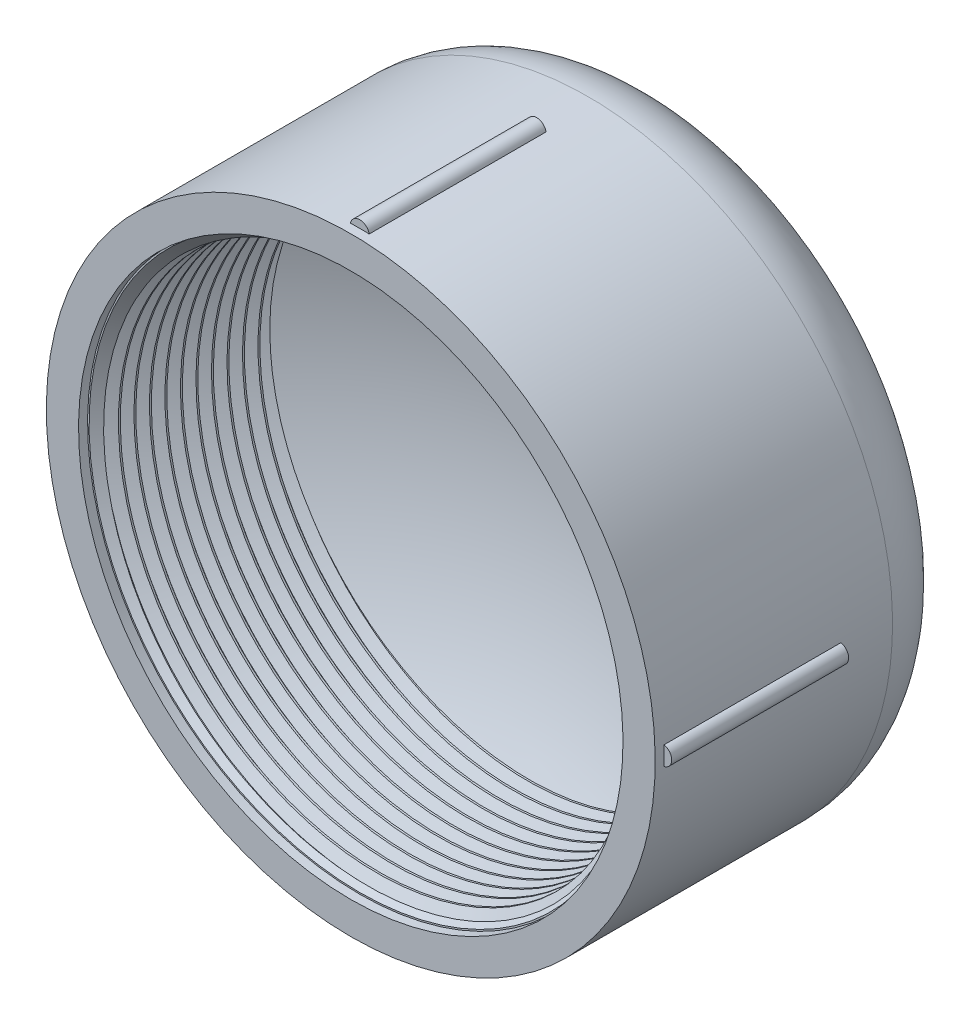
SolidWorks part; units mm, degrees
ref_plane "Front Plane" through (0, 0, 0) normal (0, 0, 1) x (1, 0, 0)
ref_plane "Top Plane" through (0, 0, 0) normal (0, 1, 0) x (1, 0, 0)
ref_plane "Right Plane" through (0, 0, 0) normal (1, 0, 0) x (0, 0, -1)
sketch "Sketch1" plane through (0, 0, 0) normal (1, 0, 0) x (0, 0, -1)
  line L0 (-37.719, 0) -> (37.719, 0) construction
  line L2 (-37.719, -57.4675) -> (-37.719, -64.262) construction
  line L3 (0.5524, 55.6734) -> (-0.381, 55.6734) construction
  line L4 (-0.381, 55.6734) -> (-0.381, 56.0468) construction
  line L5 (-37.719, -64.262) -> (22.6314, -64.262) construction
  line L6 (-37.719, 57.4675) -> (-37.719, 64.262) construction
  line L7 (-37.719, 64.262) -> (22.6314, 64.262) construction
  line L10 (0.5524, -55.6734) -> (-0.381, -55.6734) construction
  line L11 (-0.381, -55.6734) -> (-0.381, -56.0468) construction
  line L12 (-35.814, -57.15) -> (-0.381, -56.0468) construction
  line L13 (-35.814, 57.15) -> (-0.381, 56.0468) construction
  line L14 (-0.381, -55.6734) -> (-0.381, 55.6734) construction
  line L15 (-37.719, 57.4675) -> (-40.894, 57.4675) construction
  line L16 (-35.814, -57.15) -> (-35.814, -57.4675) construction
  line L17 (-35.814, -57.4675) -> (-37.719, -57.4675) construction
  line L18 (-35.814, 57.15) -> (-35.814, 57.4675) construction
  line L19 (-35.814, 57.4675) -> (-37.719, 57.4675) construction
  line L20 (-35.814, -57.15) -> (-35.814, 57.15) construction
  line L21 (-37.719, -57.4675) -> (-37.719, 0) construction
  line L22 (-37.719, 0) -> (-37.719, 57.4675) construction
  arc A0 (0.5524, -55.6734) -> (0.5524, 55.6734) centre (-106.6791, 0) ccw construction
  arc A5 (22.6314, -64.262) -> (22.6314, 64.262) centre (-106.6791, 0) ccw construction
  point P4 (0, 0)
  point P9 (-37.719, 0)
  point P30 (-35.814, 0)
  dimension "D1" = 1.783
  dimension "D2" = 1.783
  dimension "OD" = 128.524
  dimension "Body Cylindrical Length" = 60.3504
  dimension "D4" = 0.3734
  dimension "D5" = 0.9335
  dimension "NPT Pitch" = 3.175
  dimension "Thread OD" = 114.3
  dimension "Pilot Depth" = 1.905
  dimension "Pilot Dia" = 114.935
  dimension "Depth" = 37.338
  dimension "OAL" = 75.438
sketch "Sketch2" plane through (0, 0, 0) normal (1, 0, 0) x (0, 0, -1)
  line L21 (-37.719, -64.262) -> (22.6314, -64.262) construction
  line L22 (0.5524, -55.6734) -> (-0.381, -55.6734) construction
  line L23 (-0.381, -55.6734) -> (-0.381, -56.0468) construction
  line L24 (-35.814, -57.15) -> (-0.381, -56.0468) construction
  line L25 (-35.814, -57.15) -> (-35.814, -57.4675) construction
  line L26 (-35.814, -57.4675) -> (-37.719, -57.4675) construction
  line L27 (-37.719, -57.4675) -> (-37.719, -64.262) construction
  line L28 (-37.719, -64.262) -> (22.6314, -64.262)
  line L29 (0.5524, -55.6734) -> (-0.381, -55.6734)
  line L30 (-0.381, -55.6734) -> (-0.381, -56.0468)
  line L31 (-35.814, -57.15) -> (-0.381, -56.0468)
  line L32 (-35.814, -57.15) -> (-35.814, -57.4675)
  line L33 (-35.814, -57.4675) -> (-37.719, -57.4675)
  line L34 (-37.719, -57.4675) -> (-37.719, -64.262)
  line L35 (14.1436, 0) -> (37.719, 0)
  arc A1 (22.6314, -64.262) -> (22.6314, 64.262) centre (-106.6791, 0) ccw construction
  arc A2 (0.5524, -55.6734) -> (0.5524, 55.6734) centre (-106.6791, 0) ccw construction
  arc A6 (22.6314, -64.262) -> (37.719, 0) centre (-106.6791, 0) ccw
  arc A7 (0.5524, -55.6734) -> (14.1436, 0) centre (-106.6791, 0) ccw
revolve "Revolve1" add sketch "Sketch2" angle 360 about L0
fillet "Fillet1" radius 15.875 1 edges at (0, -64.262, -22.6314)
sketch "Sketch3" plane through (0, 0, 37.719) normal (0, 0, 1) x (1, 0, 0)
  circle A5 centre (0, 0) radius 57.15
  point P2 (0, 57.15)
  point P3 (-57.15, 0)
  point P4 (0, -57.15)
  point P5 (57.15, 0)
  dimension "D1" = 114.3
ref_plane "Plane1" through (0, 0, 35.814) normal (0, 0, 1) x (1, 0, 0)
sketch "Sketch4" plane through (0, 0, 35.814) normal (0, 0, 1) x (1, 0, 0)
  line L0 (-1.9844, 64.2314) -> (1.9844, 64.2314) construction
  line L1 (0, -64.262) -> (0, 64.262) construction
  line L3 (0, 64.262) -> (0, 65.8495) construction
  circle A0 centre (0, 0) radius 64.262 construction
  arc A1 (1.9844, 64.2314) -> (-1.9844, 64.2314) centre (0, 0) ccw
  arc A8 (-1.9844, 64.2314) -> (1.9844, 64.2314) centre (0, 63.8237) cw
  point P18 (0, 64.262)
  dimension "Rib Dia" = 3.9688
  dimension "Rib Height" = 1.5875
extrude "Boss-Extrude1" add sketch "Sketch4" against normal blind 37.338
pattern_circular "CirPattern1" count 4 over 360 about axis through (0, 0, 0) along (0, 0, 1) of "Boss-Extrude1"
sketch "Sketch5" plane through (0, 0, 35.814) normal (0, 0, 1) x (1, 0, 0)
  circle A1 centre (0, 0) radius 57.4675
  circle A2 centre (0, 0) radius 57.4675 construction
extrude "Boss-Extrude2" add sketch "Sketch5" against normal up to surface (35.433 mm away) contours A1 up to face at (0, -56.0468, 0.381)
sketch "Sketch6" plane through (0, 0, 35.814) normal (0, 0, 1) x (1, 0, 0)
  circle A0 centre (0, 0) radius 57.15
  dimension "D1" = 114.3
extrude "Boss-Extrude3" add sketch "Sketch6" against normal blind 35.433 draft 1.783 separate body
sketch "Sketch7" plane through (0, 0, 35.814) normal (0, 0, 1) x (1, 0, 0)
  circle A1 centre (0, 0) radius 57.15
  circle A2 centre (0, 0) radius 57.15
  dimension "D1" = 0
curve "Helix/Spiral1"
sketch "Sketch8" plane through (0, 0, 0) normal (1, 0, 0) x (0, 0, -1)
  line L0 (-38.5921, 57.15) -> (-37.4015, 55.0878) construction
  line L1 (-37.4015, 55.0878) -> (-37.0046, 55.0878)
  line L2 (-37.0046, 55.0878) -> (-35.814, 57.15) construction
  line L3 (-35.814, 57.15) -> (-38.5921, 57.15) construction
  line L4 (-37.2031, 57.15) -> (-37.2031, 55.0878) construction
  line L5 (-37.9968, 56.1189) -> (-36.4093, 56.1189) construction
  line L6 (-37.0046, 55.0878) -> (-34.6234, 59.2122)
  line L7 (-37.4015, 55.0878) -> (-39.7827, 59.2122)
  line L8 (-39.7827, 59.2122) -> (-34.6234, 59.2122)
  line L9 (-0.381, 56.0468) -> (-35.814, 57.15) construction
  line L10 (-35.814, 57.15) -> (-35.814, -57.15) construction
  dimension "D1" = 60
  dimension "D2" = 0.3969
  dimension "D3" = 1.5875
sweep "Cut-Sweep1" cut profiles "Sketch8" path "Helix/Spiral1"
combine bodies "Combine1" operation type subtract main body 108 bodies to subtract 110
sketch "Sketch9" plane through (0, 0, 0) normal (1, 0, 0) x (0, 0, -1)
  line L0 (-35.814, 57.15) -> (-30.5768, 51.9128)
  line L2 (-30.5768, 51.9128) -> (-35.814, 51.9128)
  line L4 (-35.814, 51.9128) -> (-35.814, 57.15)
  line L6 (-37.4015, 55.0878) -> (-37.0046, 55.0878) construction
  dimension "D1" = 3.175
  dimension "D2" = 45
revolve "Cut-Revolve1" cut sketch "Sketch9" angle 360 about L0
equation "\"D4@Sketch1\"=\"Depth@Sketch1\"*0.01"
equation "\"D1@Sketch3\"=\"Thread OD@Sketch1\""
equation "\"D1@Sketch6\"=\"Thread OD@Sketch1\""
equation "\"D4@Helix/Spiral1\"=\"NPT Pitch@Sketch1\""
equation "\"D2@Sketch8\"=\"D4@Helix/Spiral1\"*0.125"
equation "\"D3@Sketch8\"=\"D4@Helix/Spiral1\"*0.5"
equation "\"D5@Sketch1\"=\"Depth@Sketch1\"*0.025"
equation "\"D1@Boss-Extrude3\"=\"Depth@Sketch1\"-\"Pilot Depth@Sketch1\""
equation "\"D3@Helix/Spiral1\"=\"Depth@Sketch1\"-\"Pilot Depth@Sketch1\"+\"NPT Pitch@Sketch1\"+.02"
